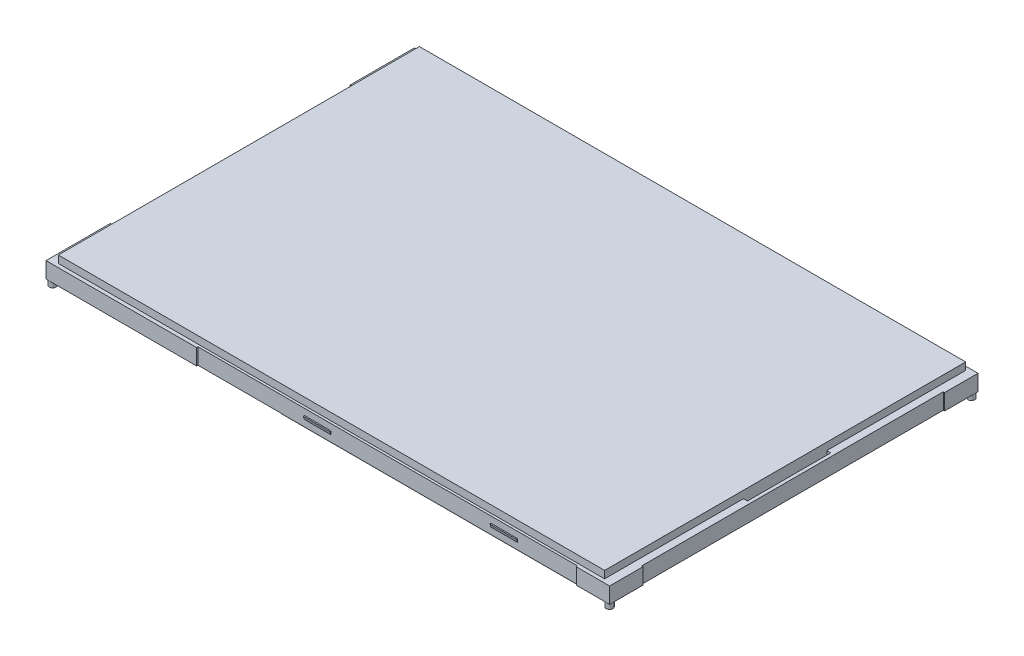
SolidWorks part; units mm, degrees
material "ABS"
ref_plane "Front" through (0, 0, 0) normal (0, 0, 1) x (1, 0, 0)
ref_plane "Top" through (0, 0, 0) normal (0, 1, 0) x (1, 0, 0)
ref_plane "Right" through (0, 0, 0) normal (1, 0, 0) x (0, 0, -1)
sketch "Sketch1" plane through (0, 0, 0) normal (0, 1, 0) x (1, 0, 0)
  line L1 (-42.3, -27.65) -> (42.3, -27.65)
  line L2 (-42.3, -27.65) -> (-42.3, 27.65)
  line L3 (-42.3, 27.65) -> (42.3, 27.65)
  line L4 (42.3, -27.65) -> (42.3, 27.65)
  line L5 (-42.3, -27.65) -> (42.3, 27.65) construction
  line L6 (-42.3, 27.65) -> (42.3, -27.65) construction
  point P0 (0, 0)
  dimension "D1" = 84.6
  dimension "D2" = 55.3
extrude "Boss-Extrude1" add sketch "Sketch1" against normal blind 2.4
sketch "Sketch2" plane through (0, 0, 0) normal (0, 1, 0) x (1, 0, 0)
  line L1 (-41, -27.1) -> (41, -27.1)
  line L2 (-41, -27.1) -> (-41, 27.1)
  line L3 (-41, 27.1) -> (41, 27.1)
  line L4 (41, -27.1) -> (41, 27.1)
  line L5 (-41, -27.1) -> (41, 27.1) construction
  line L6 (-41, 27.1) -> (41, -27.1) construction
  point P0 (0, 0)
  dimension "D1" = 82
  dimension "D2" = 54.2
extrude "Boss-Extrude2" add sketch "Sketch2" along normal blind 1.1
sketch "Sketch3" plane through (0, -2.4, 0) normal (0, -1, 0) x (1, 0, 0)
  line L0 (-42.3, 27.65) -> (42.3, 27.65) construction
  line L1 (-42.3, -27.65) -> (-42.3, 27.65) construction
  line L2 (42.3, -27.65) -> (-42.3, -27.65) construction
  line L3 (42.3, 27.65) -> (42.3, -27.65) construction
  circle A0 centre (-41.8, 27.15) radius 0.5
  circle A1 centre (41.8, 27.15) radius 0.5
  circle A2 centre (41.8, -27.15) radius 0.5
  circle A3 centre (-41.8, -27.15) radius 0.5
  dimension "D1" = 0.5
  dimension "D2" = 0.5
  dimension "D3" = 0.5
  dimension "D4" = 0.5
  dimension "D6" = 0.5
  dimension "D7" = 0.5
  dimension "D8" = 0.5
  dimension "D9" = 1
  dimension "D10" = 1
  dimension "D11" = 1
  dimension "D12" = 1
  dimension "D5" = 0.5
extrude "Boss-Extrude3" add sketch "Sketch3" along normal blind 0.8
sketch "Sketch4" plane through (0, -2.4, 0) normal (0, -1, 0) x (1, 0, 0)
  line L0 (0, 0) -> (-59.8368, 0) construction
  line L1 (-42.3, -27.15) -> (-42.3, 27.15) construction
  line L2 (-39.7, -22.4) -> (-41.3, -22.4)
  line L3 (-39.1, -21.8) -> (-39.1, 21.8)
  line L4 (-39.7, 22.4) -> (-41.3, 22.4)
  line L5 (-41.9, -21.8) -> (-41.9, 21.8)
  line L6 (-39.1, -22.4) -> (-41.9, 22.4) construction
  line L7 (-39.1, 22.4) -> (-41.9, -22.4) construction
  arc A0 (-39.7, -22.4) -> (-39.1, -21.8) centre (-39.7, -21.8) ccw
  arc A1 (-41.3, -22.4) -> (-41.9, -21.8) centre (-41.3, -21.8) cw
  arc A2 (-39.1, 21.8) -> (-39.7, 22.4) centre (-39.7, 21.8) ccw
  arc A3 (-41.3, 22.4) -> (-41.9, 21.8) centre (-41.3, 21.8) ccw
  point P3 (-40.5, 0)
  dimension "D4" = 0.6
  dimension "D1" = 2.8
  dimension "D2" = 44.8
  dimension "D3" = 0.4
extrude "Cut-Extrude1" cut sketch "Sketch4" against normal blind 1
sketch "Sketch5" plane through (0, 0, 27.65) normal (0, 0, 1) x (1, 0, 0)
  line L0 (-41, 0) -> (41, 0) construction
  line L1 (-19.7, 0) -> (37.3, 0)
  line L2 (-19.7, 0) -> (-19.7, -2.4)
  line L3 (-19.7, -2.4) -> (37.3, -2.4)
  line L4 (37.3, 0) -> (37.3, -2.4)
  line L5 (-41.8, -2.4) -> (41.8, -2.4) construction
  line L6 (-42.3, -2.4) -> (-42.3, 0) construction
  line L7 (42.3, -2.4) -> (42.3, 0) construction
  point P8 (-42.3, -1.2)
  point P11 (42.3, -1.2)
  dimension "D1" = 22.6
  dimension "D2" = 5
extrude "Cut-Extrude2" cut sketch "Sketch5" against normal blind 0.2
mirror "Mirror1" about plane through (0, 0, 0) normal (0, 0, 1) of "Cut-Extrude2"
sketch "Sketch6" plane through (42.3, 0, 0) normal (1, 0, 0) x (0, 0, -1)
  line L0 (-27.65, 0) -> (27.65, 0) construction
  line L1 (-22.65, 0) -> (22.65, 0)
  line L2 (-22.65, 0) -> (-22.65, -2.4)
  line L3 (-22.65, -2.4) -> (22.65, -2.4)
  line L4 (22.65, 0) -> (22.65, -2.4)
  line L5 (-27.15, -2.4) -> (27.15, -2.4) construction
  line L6 (-27.65, 0) -> (-27.65, -2.4) construction
  line L7 (27.65, -2.4) -> (27.65, 0) construction
  point P8 (-27.65, -1.2)
  point P11 (27.65, -1.2)
  dimension "D1" = 5
  dimension "D2" = 5
extrude "Cut-Extrude3" cut sketch "Sketch6" against normal blind 0.2
sketch "Sketch7" plane through (0, -2.4, 0) normal (0, -1, 0) x (1, 0, 0)
  line L0 (-19.7, 27.45) -> (37.3, 27.45) construction
  line L1 (-7.3, 27.35) -> (37.3, 27.35)
  line L2 (-7.3, 27.35) -> (-7.3, 24.35)
  line L3 (-7.3, 24.35) -> (37.3, 24.35)
  line L4 (37.3, 27.35) -> (37.3, 24.35)
  line L5 (42.3, 27.15) -> (42.3, 22.65) construction
  line L6 (-42.3, -27.15) -> (-42.3, 27.15) construction
  dimension "D1" = 3
  dimension "D2" = 0.1
  dimension "D3" = 5
  dimension "D4" = 35
extrude "Boss-Extrude4" add sketch "Sketch7" along normal blind 0.15
mirror "Mirror2" about plane through (0, 0, 0) normal (0, 0, 1) of "Boss-Extrude4"
sketch "Sketch8" plane through (0, 0, 0) normal (0, 1, 0) x (1, 0, 0)
  line L0 (41, 0) -> (42.1, 0) construction
  line L1 (41, -27.1) -> (41, 27.1) construction
  line L2 (42.1, 22.65) -> (42.1, -22.65) construction
  line L3 (41, -27.1) -> (41, 27.1) construction
  line L4 (41.6, -6.25) -> (41, -6.25)
  line L5 (41.6, -6.25) -> (41.6, 6.25)
  line L6 (41.6, 6.25) -> (41, 6.25)
  line L7 (41, -6.25) -> (41, 6.25)
  line L8 (41.6, -6.25) -> (41, 6.25) construction
  line L9 (41.6, 6.25) -> (41, -6.25) construction
  point P6 (41.3, 0)
  dimension "D1" = 12.5
  dimension "D2" = 0.6
extrude "Cut-Extrude4" cut sketch "Sketch8" against normal blind 1
sketch "Sketch9" plane through (0, 0, 27.45) normal (0, 0, 1) x (1, 0, 0)
  line L0 (-19.7, -1.2) -> (37.3, -1.2) construction
  line L1 (-19.7, 0) -> (-19.7, -2.4) construction
  line L2 (37.3, -2.4) -> (37.3, 0) construction
  line L4 (0.3, -1.45) -> (-3.7, -1.45)
  line L5 (0.3, -1.45) -> (0.3, -0.95)
  line L6 (0.3, -0.95) -> (-3.7, -0.95)
  line L7 (-3.7, -1.45) -> (-3.7, -0.95)
  line L8 (0.3, -1.45) -> (-3.7, -0.95) construction
  line L9 (0.3, -0.95) -> (-3.7, -1.45) construction
  line L10 (28.3, -1.45) -> (24.3, -1.45)
  line L11 (28.3, -1.45) -> (28.3, -0.95)
  line L12 (28.3, -0.95) -> (24.3, -0.95)
  line L13 (24.3, -1.45) -> (24.3, -0.95)
  line L14 (28.3, -1.45) -> (24.3, -0.95) construction
  line L15 (28.3, -0.95) -> (24.3, -1.45) construction
  point P6 (-1.7, -1.2)
  point P11 (26.3, -1.2)
  dimension "D1" = 0.5
  dimension "D2" = 4
  dimension "D3" = 18
  dimension "D4" = 4
  dimension "D5" = 0.5
  dimension "D6" = 11
extrude "Boss-Extrude5" add sketch "Sketch9" along normal blind 0.2
chamfer "Chamfer1" distance 0.2 angle 70 2 edges at (26.3, -1.45, 27.65) (-1.7, -1.45, 27.65) first distance on face at (26.3, -1.45, 27.55) first distance on face at (-1.7, -1.45, 27.55)
mirror "Mirror4" about plane through (0, 0, 0) normal (0, 0, 1) of "Boss-Extrude5", "Chamfer1"
sketch "Sketch10" plane through (-42.3, 0, 0) normal (-1, 0, 0) x (0, 0, 1)
  line L0 (-27.1, 0) -> (27.1, 0) construction
  line L1 (-18, -1.5) -> (18, -1.5)
  line L2 (-18, -1.5) -> (-18, 0)
  line L3 (-18, 0) -> (18, 0)
  line L4 (18, -1.5) -> (18, 0)
  line L5 (-18, -1.5) -> (18, 0) construction
  line L6 (-18, 0) -> (18, -1.5) construction
  line L7 (0, 0) -> (0, -2.4) construction
  line L8 (-27.15, -2.4) -> (27.15, -2.4) construction
  point P0 (0, -0.75)
  dimension "D1" = 1.5
  dimension "D2" = 36
  dimension "D3" = 0
extrude "Cut-Extrude5" cut sketch "Sketch10" against normal blind 10
sketch "Sketch12" plane through (-32.3, 0, 0) normal (-1, 0, 0) x (0, 0, 1)
  line L0 (0, 0) -> (0, -1.5) construction
  line L1 (-18, -1.5) -> (18, -1.5) construction
  line L2 (-18, -0.75) -> (18, -0.75) construction
  line L3 (-18, 0) -> (-18, -1.5) construction
  line L4 (18, -1.5) -> (18, 0) construction
sketch "Sketch13" plane through (0, 0, 0) normal (0, 0, 1) x (1, 0, 0)
  line L0 (-32.3, -0.75) -> (-42.05, -0.75)
  line L1 (-32.3, 0) -> (-32.3, -1.5) construction
  line L2 (-42.05, -2.7) -> (-27.3, -4.65)
  line L3 (-17.3, -7.65) -> (-4.8, -7.65)
  line L4 (-3.8, -7.75) -> (-4.8, -7.75) construction
  line L6 (-32.3, -0.65) -> (-42.0564, -0.65)
  line L7 (-42.0631, -2.7991) -> (-27.3146, -4.7489)
  line L8 (-17.3, -7.75) -> (-4.8, -7.75)
  line L9 (-32.3, -0.85) -> (-42.0432, -0.85)
  line L10 (-42.0369, -2.6009) -> (-27.2854, -4.5511)
  line L11 (-17.3, -7.55) -> (-4.8, -7.55)
  line L12 (-32.3, -0.65) -> (-32.3, -0.85)
  line L13 (-4.8, -7.55) -> (-4.8, -7.75)
  line L14 (-27.3, -5.15) -> (-27.3, -6.75) construction
  line L15 (-4.8, -7.75) -> (-4.8, -6.75) construction
  line L16 (-17.3, -5.15) -> (-17.3, -6.75) construction
  line L17 (-41.8, -2.4) -> (-19.7, -2.4) construction
  arc A0 (-42.05, -0.75) -> (-42.05, -2.7) centre (-41.9211, -1.725) ccw
  arc A1 (-42.0564, -0.65) -> (-42.0631, -2.7991) centre (-41.9211, -1.725) ccw
  arc A2 (-42.0432, -0.85) -> (-42.0369, -2.6009) centre (-41.9211, -1.725) ccw
  spline S0 degree 3 poles (-27.3, -4.65) (-22.9195, -5.3641) (-22.9508, -7.5753) (-17.3, -7.65) knots 0 0 0 0 1 1 1 1
  spline S1 degree 1 poles (-27.3146, -4.7489) (-17.3, -7.75) knots 0 0 1 1 construction
  spline S2 degree 3 poles (-27.3146, -4.7489) (-27.058, -4.7908) (-26.5274, -4.8945) (-25.6389, -5.1322) (-24.6936, -5.4923) (-23.739, -5.9791) (-22.8331, -6.4831) (-21.8603, -6.9609) (-20.8973, -7.2989) (-19.9784, -7.5107) (-19.2015, -7.6349) (-18.4657, -7.7052) (-17.8237, -7.7388) (-17.472, -7.7477) (-17.3, -7.75) knots 0.000114 0.000114 0.000114 0.000114 0.062612 0.125109 0.250105 0.3751 0.500096 0.625091 0.750087 0.812585 0.875082 0.93758 0.968829 1.000078 1.000078 1.000078 1.000078
  spline S3 degree 1 poles (-27.2854, -4.5511) (-17.3, -7.55) knots 0 0 1 1 construction
  spline S4 degree 3 poles (-27.2854, -4.5511) (-27.0244, -4.5936) (-26.4853, -4.6988) (-25.5791, -4.9409) (-24.613, -5.3087) (-23.6439, -5.8032) (-22.7392, -6.3064) (-21.7835, -6.7757) (-20.843, -7.106) (-19.9426, -7.3138) (-19.1789, -7.4361) (-18.4532, -7.5055) (-17.8186, -7.5388) (-17.4703, -7.5477) (-17.3, -7.55) knots -0.000113 -0.000113 -0.000113 -0.000113 0.062389 0.124891 0.249895 0.3749 0.499904 0.624909 0.749913 0.812415 0.874917 0.937419 0.968671 0.999922 0.999922 0.999922 0.999922
  dimension "D2" = 9.75
  dimension "D3" = 0.1
  dimension "D4" = 0
  dimension "D5" = 0
  dimension "D6" = 0
  dimension "D7" = 0
  dimension "D8" = 0
  dimension "D9" = 0.1
  dimension "D10" = 0.5
  dimension "D11" = 0.3
extrude "Boss-Extrude7" add sketch "Sketch13" along normal blind 12.5 and the other way blind 12.5 contours L7 S2 L8 L13 L3 S0 L2 A0 L0 L12 L6 A1 | S4 L10 A2 L9 L12 L0 A0 L2 S0 L3 L13 L11 region at (-32.6872, -0.8, 0) region at (-37.175, -0.7111, 0)
